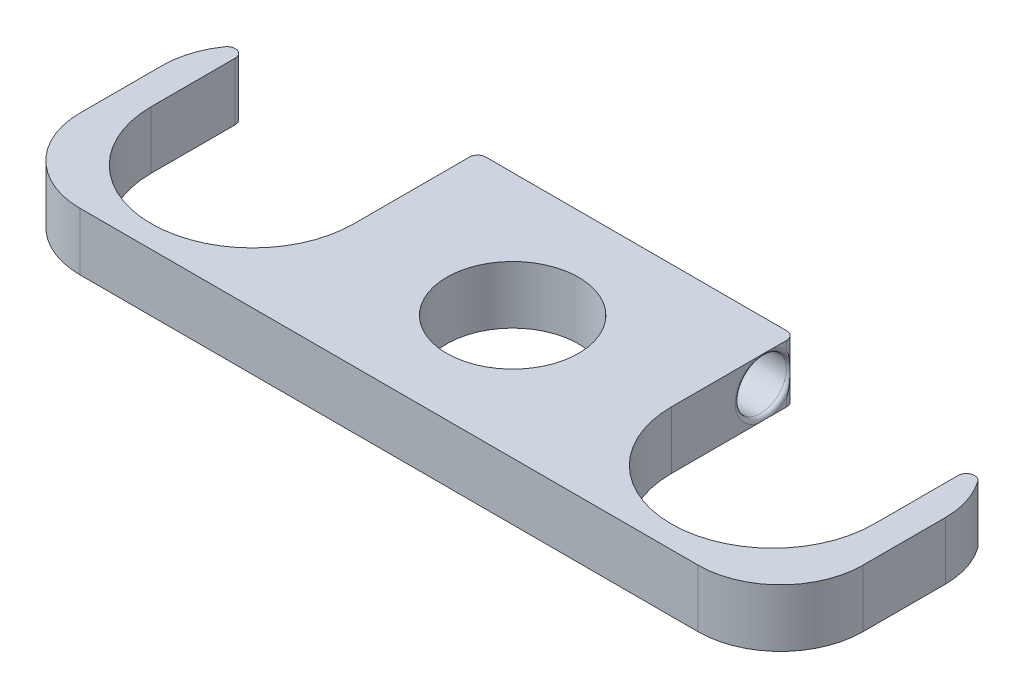
SolidWorks part; units mm, degrees
material "PLA"
ref_plane "Front Plane" through (0, 0, 0) normal (0, 0, 1) x (1, 0, 0)
ref_plane "Top Plane" through (0, 0, 0) normal (0, 1, 0) x (1, 0, 0)
ref_plane "Right Plane" through (0, 0, 0) normal (1, 0, 0) x (0, 0, -1)
sketch "Sketch1" plane through (0, 0, 0) normal (0, 1, 0) x (1, 0, 0)
  line L0 (0, 15) -> (0, -15) construction
  line L1 (-37.5, -15) -> (37.5, -15)
  line L2 (-47.5, -5) -> (-47.5, 5)
  line L3 (-37.5, 15) -> (37.5, 15)
  line L4 (47.5, -5) -> (47.5, 5)
  line L5 (-47.5, 0) -> (47.5, 0) construction
  line L7 (-47.5, 15) -> (0, 15) construction
  line L8 (0, 15) -> (-23.75, 15) construction
  circle A0 centre (0, 0) radius 8
  arc A2 (37.5, 15) -> (47.5, 5) centre (37.5, 5) cw
  arc A3 (37.5, -15) -> (47.5, -5) centre (37.5, -5) ccw
  arc A4 (-37.5, -15) -> (-47.5, -5) centre (-37.5, -5) cw
  arc A5 (-47.5, 5) -> (-37.5, 15) centre (-37.5, 5) cw
  point P0 (0, 0)
  point P17 (47.5, -15)
  point P20 (-47.5, -15)
  dimension "D3" = 16
  dimension "D5" = 10
  dimension "D1" = 30
  dimension "D2" = 95
extrude "Boss-Extrude1" add sketch "Sketch1" along normal blind 7
sketch "Sketch2" plane through (0, 7, 0) normal (0, 1, 0) x (1, 0, 0)
  line L1 (-19.25, 0) -> (-19.25, 15)
  line L2 (37.5, 15) -> (-37.5, 15) construction
  line L7 (-43.85, 0) -> (-43.85, 15)
  line L9 (-14.25, 0) -> (-19.25, 0) construction
  line L10 (-47.5, 0) -> (47.5, 0) construction
  line L11 (-47.5, 5) -> (-47.5, -5) construction
  line L12 (47.5, -5) -> (47.5, 5) construction
  line L13 (-43.85, 15) -> (-19.25, 15)
  circle A0 centre (-31.55, 0) radius 12.3 construction
  circle A1 centre (0, 0) radius 14.25 construction
  arc A3 (-43.85, 0) -> (-19.25, 0) centre (-31.55, 0) ccw
  dimension "D1" = 24.6
  dimension "D2" = 28.5
  dimension "D3" = 5
ref_axis "Axis1" through (0, 0, 0) along (0, 1, 0)
ref_plane "Plane1" through (0, 0, 0) normal (-1, 0, 0) x (0, 1, 0)
extrude "Cut-Extrude1" cut sketch "Sketch2" against normal blind 10
sketch "Sketch3" plane through (-19.25, 0, 0) normal (-1, 0, 0) x (0, 0, 1)
  line L0 (-15, 3.5) -> (0, 3.5) construction
  line L1 (-15, 0) -> (-15, 7) construction
  line L2 (0, 0) -> (0, 32.876) construction
  line L3 (0, 3.5) -> (-11.3487, 7) construction
  line L4 (0, 7) -> (-15, 7) construction
  line L5 (-11.3487, 7) -> (-11.3487, 0) construction
  line L6 (-15, 0) -> (0, 0) construction
  circle A0 centre (-11.3487, 3.5) radius 3.1
  point P14 (-11.3487, 3.5)
  dimension "D1" = 6.2
extrude "Cut-Extrude2" cut sketch "Sketch3" against normal blind 6
fillet "Fillet1" radius 0.5 1 edges at (-19.25, 3.5, -8.2487) type face fillet first side face at (-13.25, 3.5, -8.2487) second side face at (-19.25, 3.5, -8.2487)
fillet "Fillet2" radius 1 1 edges at (-43.85, 3.5, -12.7251) type face fillet first side face at (-43.85, 3.5, -6.3626) second side face at (-46.1083, 3.5, -9.0673)
fillet "Fillet3" radius 1 1 edges at (-19.25, 3.5, -15) type face fillet first side face at (-19.25, 3.5, -14.285) second side face at (9.125, 3.5, -15)
mirror "Mirror5" about plane through (0, 0, 0) normal (-1, 0, 0) of "Cut-Extrude2", "Cut-Extrude1"
fillet "Fillet5" radius 1 1 edges at (43.85, 3.5, -12.7251) type face fillet first side face at (43.85, 3.5, -6.3626) second side face at (46.1083, 3.5, -9.0673)
fillet "Fillet6" radius 0.5 1 edges at (19.25, 3.5, -8.2487) type face fillet first side face at (13.25, 3.5, -8.2487) second side face at (19.25, 3.5, -8.2487)
fillet "Fillet7" radius 1 1 edges at (19.25, 3.5, -15) type face fillet first side face at (19.25, 3.5, -14.285) second side face at (0.5, 3.5, -15)
